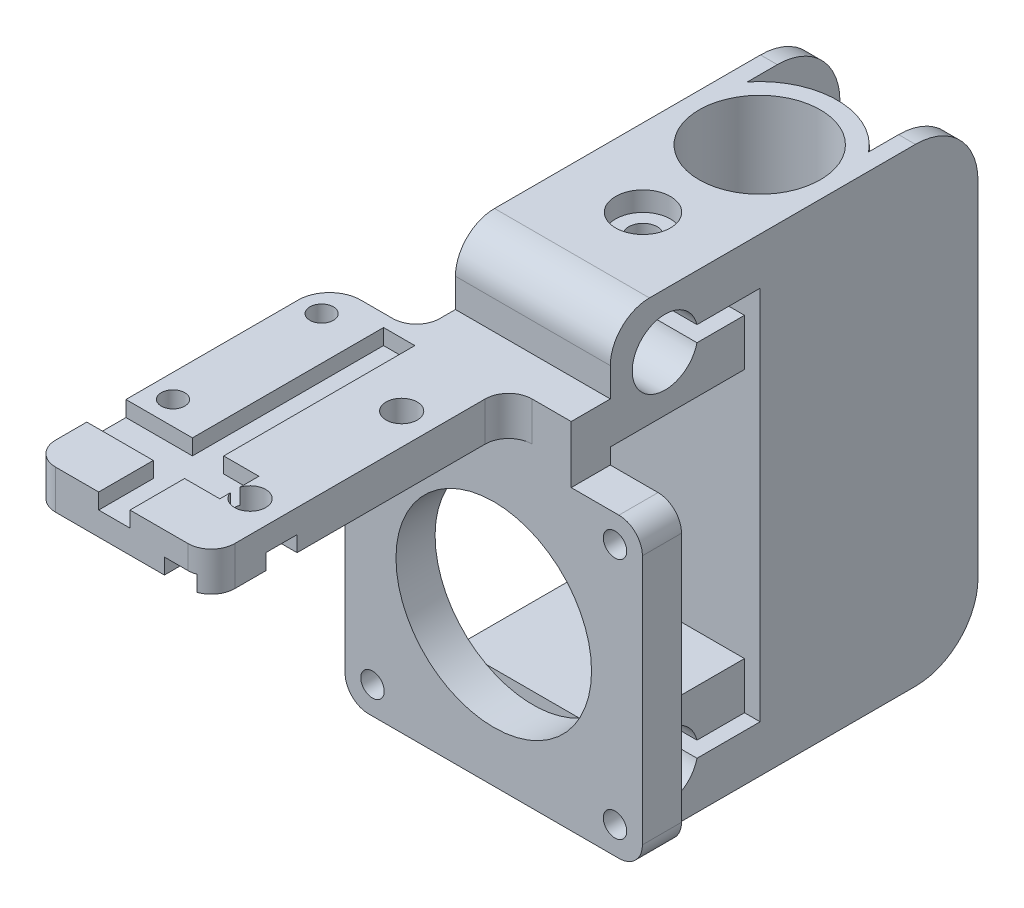
SolidWorks part; units mm, degrees
ref_plane "Спереди" through (0, 0, 0) normal (0, 0, 1) x (1, 0, 0)
ref_plane "Сверху" through (0, 0, 0) normal (0, 1, 0) x (1, 0, 0)
ref_plane "Справа" through (0, 0, 0) normal (1, 0, 0) x (0, 0, -1)
sketch "Эскиз1" plane through (0, 0, 0) normal (0, 1, 0) x (1, 0, 0)
  line L0 (9.9, 0) -> (9.9, 18)
  line L1 (9.9, 18) -> (-9.9, 18)
  line L2 (-9.9, 18) -> (-9.9, 0)
  line L3 (-9.9, 0) -> (-9.9, -29)
  line L4 (-9.9, -29) -> (9.9, -29)
  line L5 (9.9, -29) -> (9.9, 0)
  line L7 (-7.75, -23.1528) -> (7.75, -23.1528)
  line L8 (-7.75, -23.1528) -> (-7.75, 14)
  line L9 (-7.75, 14) -> (7.75, 14)
  line L10 (7.75, -23.1528) -> (7.75, 14)
  line L11 (-7.75, -9.9) -> (7.75, -9.9)
  line L12 (-7.75, -9.9) -> (-7.75, -11.85)
  line L13 (-7.75, -11.85) -> (7.75, -11.85)
  line L14 (7.75, -9.9) -> (7.75, -11.85)
  circle A0 centre (0, 0) radius 7.75
  circle A2 centre (0, 0) radius 9.9
  point P18 (0, -9.9)
  dimension "D1" = 15.5
  dimension "D2" = 19.8
  dimension "D4" = 2.15
  dimension "D3" = 18
  dimension "D5" = 1.95
  dimension "D6" = 47
  dimension "D7" = 4
extrude "Бобышка-Вытянуть1" add sketch "Эскиз1" along normal blind 60 contours L10 A2 L8 A0 | A2 L0 L1 L2 L8 L9 L10 | L10 A2 | L8 A2 | A2 L10 A0 L8 | A2 L10 L7 L8 L3 L4 L5 | L13 L8 L7 L10 | L8 L13 L10 L11 | A2 L11 L10 | A2 L8 L11
sketch "Эскиз2" plane through (9.9, 0, 0) normal (1, 0, 0) x (0, 0, -1)
  line L0 (-29, 60) -> (-29, 0) construction
  line L1 (-29, 60) -> (18, 60) construction
  line L2 (-29, 0) -> (18, 0) construction
  circle A0 centre (-22, 53) radius 4.2
  circle A1 centre (-22, 7) radius 4.2
  dimension "D1" = 8.4
  dimension "D2" = 7
  dimension "D3" = 7
  dimension "D4" = 7
extrude "Вырез-Вытянуть1" cut sketch "Эскиз2" against normal blind 90
sketch "Эскиз3" plane through (9.9, 0, 0) normal (1, 0, 0) x (0, 0, -1)
  line L1 (-29, 60) -> (-29, 0) construction
  line L2 (-29, 0) -> (18, 0) construction
  line L3 (-29, 60) -> (18, 60) construction
  line L5 (-33.0715, 30) -> (18, 30) construction
  line L10 (18, 60) -> (18, 0) construction
  line L26 (-22, 6) -> (-9.85, 6)
  line L27 (-22, 6) -> (-22, 8)
  line L28 (-22, 8) -> (-9.85, 8)
  line L29 (-9.85, 6) -> (-9.85, 8)
  line L30 (-22, 52) -> (-9.85, 52)
  line L31 (-22, 52) -> (-22, 54)
  line L32 (-22, 54) -> (-9.85, 54)
  line L33 (-9.85, 52) -> (-9.85, 54)
  line L34 (-9.85, 6) -> (-11.85, 6)
  line L35 (-9.85, 6) -> (-9.85, 54)
  line L36 (-9.85, 54) -> (-11.85, 54)
  line L37 (-11.85, 6) -> (-11.85, 54)
  line L38 (-9.85, 14) -> (-29, 14)
  line L39 (-9.85, 14) -> (-9.85, 46)
  line L40 (-9.85, 46) -> (-29, 46)
  line L41 (-29, 14) -> (-29, 46)
  circle A1 centre (-22, 7) radius 4.2 construction
  circle A2 centre (-22, 53) radius 4.2 construction
  point P2 (-22, 7)
  point P7 (-22, 53)
  dimension "D2" = 14
  dimension "D3" = 14
  dimension "D4" = 17.15
  dimension "D8" = 2
  dimension "D9" = 2
  dimension "D10" = 2
extrude "Вырез-Вытянуть2" cut sketch "Эскиз3" against normal blind 40
sketch "Эскиз4" plane through (0, 0, -18) normal (0, 0, -1) x (-1, 0, 0)
  line L0 (-9.9, 60) -> (9.9, 60) construction
  line L1 (-7.75, 60) -> (7.75, 60)
  line L2 (-7.75, 60) -> (-7.75, 40.5)
  line L3 (-7.75, 26.5) -> (7.75, 26.5)
  line L4 (7.75, 60) -> (7.75, 40.5)
  line L5 (-9.9, 0) -> (9.9, 0) construction
  line L6 (7.75, 26.5) -> (7.75, 33.5)
  line L7 (7.75, 33.5) -> (-7.75, 33.5)
  line L9 (7.75, 40.5) -> (-7.75, 40.5)
  line L10 (-7.75, 0) -> (7.75, 0)
  line L11 (-7.75, 0) -> (-7.75, 19.5)
  line L12 (-7.75, 19.5) -> (7.75, 19.5)
  line L13 (7.75, 0) -> (7.75, 19.5)
  line L14 (7.75, 26.5) -> (7.75, 33.5)
  line L15 (-7.75, 60) -> (-7.75, 40.5)
  line L16 (7.75, 40.5) -> (7.75, 60)
  line L17 (-7.75, 33.5) -> (-7.75, 26.5)
  line L18 (-7.75, 33.5) -> (-7.75, 26.5)
  line L19 (7.75, 33.5) -> (7.75, 26.5)
  line L20 (9.9, 60) -> (9.9, 0) construction
  point P20 (7.75, 30)
  point P23 (9.9, 30)
  line M9 (-9.9, 0) -> (9.9, 0)
  line M11 (9.9, 60) -> (-9.9, 60)
  dimension "D1" = 7
  dimension "D2" = 7
  dimension "D4" = 7
extrude "Вырез-Вытянуть3" cut sketch "Эскиз4" against normal blind 6 contours L4 L2 L3 M11 | L13 L12 L11 M9 | L7 L17 L3 L6
fillet "Скругление1" radius 5 2 edges at (0, 60, 29) (0, 0, 29)
fillet "Скругление2" radius 8 4 edges at (8.825, 0, -18) (-8.825, 0, -18) (-8.825, 60, -18) (8.825, 60, -18)
sketch "Эскиз13" plane through (0, 0, 0) normal (0, -1, 0) x (1, 0, 0)
  circle A0 centre (0, 14.9208) radius 1.8
  dimension "D1" = 3.6
  dimension "D2" = 3
extrude "Вырез-Вытянуть9" cut sketch "Эскиз13" against normal blind 75
sketch "Эскиз8" plane through (0, 0, 29) normal (0, 0, 1) x (1, 0, 0)
  line L0 (-9.9, 55) -> (-9.9, 46) construction
  line L1 (-19, 44) -> (19, 44)
  line L2 (-19, 44) -> (-19, 6)
  line L3 (-19, 6) -> (19, 6)
  line L4 (19, 44) -> (19, 6)
  line L5 (-9.9, 5) -> (9.9, 5) construction
  line L6 (9.9, 0) -> (-9.9, 0) construction
  line L7 (9.9, 44) -> (-9.9, 44)
  line L8 (9.9, 44) -> (9.9, 51.3151)
  line L9 (9.9, 51.3151) -> (-9.9, 51.3151)
  line L10 (-9.9, 44) -> (-9.9, 51.3151)
  line L11 (9.9, 55) -> (9.9, 46) construction
  point P4 (0, 6)
  point P7 (0, 5)
  line M13 (-9.9, 14) -> (-9.9, 5)
  line M15 (9.9, 5) -> (9.9, 14)
  line M16 (9.9, 14) -> (-9.9, 14)
  dimension "D1" = 38
  dimension "D2" = 38
  dimension "D3" = 6
extrude "Бобышка-Вытянуть3" add sketch "Эскиз8" along normal blind 5 contours L4 L1 L2 L3 M13 M16 M15 | L10 L1 L8 L9 | L3 M13 M15 M16
sketch "Эскиз10" plane through (0, 0, 34) normal (0, 0, 1) x (1, 0, 0)
  line L2 (-19, 44) -> (-19, 6) construction
  line L3 (-19, 6) -> (19, 6) construction
  line L4 (-15.5, 9.5) -> (-15.5, 40.5) construction
  line L5 (-15.5, 40.5) -> (15.5, 40.5) construction
  line L6 (15.5, 40.5) -> (15.5, 9.5) construction
  line L7 (15.5, 9.5) -> (-15.5, 9.5) construction
  circle A0 centre (0, 25) radius 12.5
  circle A1 centre (-15.5, 9.5) radius 1.5
  circle A2 centre (15.5, 9.5) radius 1.5
  circle A3 centre (-15.5, 40.5) radius 1.5
  circle A4 centre (15.5, 40.5) radius 1.5
  point P11 (0, 9.5)
  point P14 (-19, 25)
  point P15 (15.5, 25)
  point P17 (0, 6)
  dimension "D1" = 25
  dimension "D2" = 3
  dimension "D3" = 31
  dimension "D4" = 31
extrude "Вырез-Вытянуть6" cut sketch "Эскиз10" against normal up to vertex (5 mm away) contours A0 | A1 | A3 | A2 | A4 up to point (19, 6, 29)
fillet "Скругление4" radius 3 4 edges at (19, 44, 31.5) (-19, 44, 31.5) (-19, 6, 31.5) (19, 6, 31.5)
sketch "Эскиз14" plane through (0, 14, 0) normal (0, 1, 0) x (1, 0, 0)
  line L0 (-9.9, -11.85) -> (9.9, -11.85) construction
  line L1 (-1.7729, -17.9916) -> (1.7729, -17.9916)
  line L2 (1.7729, -17.9916) -> (3.5458, -14.9208)
  line L3 (3.5458, -14.9208) -> (1.7729, -11.85)
  line L4 (1.7729, -11.85) -> (-1.7729, -11.85)
  line L5 (-1.7729, -11.85) -> (-3.5458, -14.9208)
  line L6 (-3.5458, -14.9208) -> (-1.7729, -17.9916)
  circle A0 centre (0, -14.9208) radius 3.0708 construction
extrude "Вырез-Вытянуть10" cut sketch "Эскиз14" against normal blind 2 and the other way blind 34
sketch "Эскиз15" plane through (0, 60, 0) normal (0, 1, 0) x (1, 0, 0)
  circle A0 centre (0, -14.9208) radius 3.5
  dimension "D1" = 7
extrude "Вырез-Вытянуть11" cut sketch "Эскиз15" against normal blind 2.5
sketch "Эскиз16" plane through (0, 0, 0) normal (0, -1, 0) x (1, 0, 0)
  circle A0 centre (0, 14.9208) radius 3.5
  dimension "D1" = 7
extrude "Вырез-Вытянуть12" cut sketch "Эскиз16" against normal blind 2.5
sketch "Эскиз17" plane through (0, 0, 34) normal (0, 0, 1) x (1, 0, 0)
  line L1 (1.9, 51.3151) -> (-21, 51.3151)
  line L2 (1.9, 51.3151) -> (1.9, 46.3151)
  line L3 (1.9, 46.3151) -> (-21, 46.3151)
  line L4 (-21, 51.3151) -> (-21, 46.3151)
  line L5 (-19, 41) -> (-19, 9) construction
  line L6 (9.9, 51.3151) -> (-9.9, 51.3151) construction
  line L7 (9.9, 44) -> (9.9, 51.3151) construction
  dimension "D1" = 5
  dimension "D2" = 2
  dimension "D3" = 8
extrude "Бобышка-Вытянуть4" add sketch "Эскиз17" along normal blind 38
sketch "Эскиз18" plane through (0, 51.3151, 0) normal (0, 1, 0) x (1, 0, 0)
  line L0 (-9.9, -34) -> (-21, -34) construction
  line L1 (-21, -72) -> (-21, -34) construction
  line L2 (1.9, -72) -> (1.9, -34) construction
  circle A0 centre (-18, -57) radius 1.5
  circle A1 centre (-18, -38) radius 1.5
  circle A2 centre (-2.1, -63.0448) radius 2
  circle A3 centre (-2.1, -43.673) radius 2
  dimension "D1" = 19
  dimension "D4" = 3
  dimension "D5" = 4
  dimension "D2" = 4
  dimension "D3" = 3
  dimension "D6" = 4
extrude "Вырез-Вытянуть13" cut sketch "Эскиз18" against normal blind 36.5
sketch "Эскиз19" plane through (0, 46.3151, 0) normal (0, -1, 0) x (1, 0, 0)
  line L1 (-18, 61.0415) -> (-21.5, 59.0207)
  line L2 (-21.5, 59.0207) -> (-21.5, 54.9793)
  line L3 (-21.5, 54.9793) -> (-18, 52.9585)
  line L4 (-18, 52.9585) -> (-14.5, 54.9793)
  line L5 (-14.5, 54.9793) -> (-14.5, 59.0207)
  line L6 (-14.5, 59.0207) -> (-18, 61.0415)
  line L7 (-18, 42.0415) -> (-21.5, 40.0207)
  line L8 (-21.5, 40.0207) -> (-21.5, 35.9793)
  line L9 (-21.5, 35.9793) -> (-18, 33.9585)
  line L10 (-18, 33.9585) -> (-14.5, 35.9793)
  line L11 (-14.5, 35.9793) -> (-14.5, 40.0207)
  line L12 (-14.5, 40.0207) -> (-18, 42.0415)
  line L13 (-21, 72) -> (-21, 34) construction
  circle A0 centre (-18, 57) radius 3.5 construction
  circle A1 centre (-18, 38) radius 3.5 construction
  dimension "D1" = 7
extrude "Вырез-Вытянуть14" cut sketch "Эскиз19" against normal blind 2
fillet "Скругление5" radius 3 4 edges at (-21, 48.8151, 72) (1.9, 48.8151, 72) (1.9, 48.8151, 34) (-9.9, 48.8151, 34)
sketch "Эскиз20" plane through (0, 51.3151, 0) normal (0, 1, 0) x (1, 0, 0)
  line L0 (-1.1, -72) -> (-18, -72) construction
  line L1 (-8.5, -72) -> (-12.5, -72)
  line L2 (-8.5, -72) -> (-8.5, -35.5865)
  line L3 (-8.5, -35.5865) -> (-12.5, -35.5865)
  line L4 (-12.5, -72) -> (-12.5, -35.5865)
  line L5 (-21, -69) -> (-21, -34) construction
  line L6 (-4, -65.0182) -> (-21, -65.0182)
  line L7 (-4, -65.0182) -> (-4, -60.0182)
  line L8 (-4, -60.0182) -> (-21, -60.0182)
  line L9 (-21, -65.0182) -> (-21, -60.0182)
  line L11 (-12.9, -34) -> (-21, -34) construction
  point P14 (-16.95, -34)
  line M10 (-21, -34) -> (-21, -69)
  line M12 (-18, -72) -> (-1.1, -72)
  dimension "D1" = 31.0182
  dimension "D2" = 5
  dimension "D3" = 8.5
  dimension "D4" = 4
  dimension "D5" = 17
extrude "Вырез-Вытянуть15" cut sketch "Эскиз20" against normal blind 2 contours L7 L8 L2 L6 | L2 L8 L4 L6 | L4 L8 L6 M10 | L2 L6 L4 M12 | L8 L2 L3 L4
fillet "Скругление6" radius 4 1 edges at (-21, 48.8151, 34)
sketch "Эскиз22" plane through (0, 46.3151, 0) normal (0, -1, 0) x (1, 0, 0)
  line L0 (1.9, 69) -> (1.9, 37) construction
  line L1 (-2.1, 65.0448) -> (1.9, 65.0448)
  line L2 (-2.1, 65.0448) -> (-2.1, 61.0448)
  line L3 (-2.1, 61.0448) -> (1.9, 61.0448)
  line L4 (1.9, 65.0448) -> (1.9, 61.0448)
  line L5 (-18, 72) -> (-1.1, 72) construction
  line L6 (-2.1, 45.673) -> (1.9, 45.673)
  line L7 (-2.1, 45.673) -> (-2.1, 41.673)
  line L8 (-2.1, 41.673) -> (1.9, 41.673)
  line L9 (1.9, 45.673) -> (1.9, 41.673)
  line L10 (-4.1, 72) -> (-0.1, 72)
  line L11 (-4.1, 72) -> (-4.1, 63.0448)
  line L12 (-4.1, 63.0448) -> (-0.1, 63.0448)
  line L13 (-0.1, 72) -> (-0.1, 63.0448)
  circle A0 centre (-2.1, 63.0448) radius 2 construction
  circle A1 centre (-2.1, 43.673) radius 2 construction
  circle M4 centre (-2.1, 63.0448) radius 2
  line M13 (1.9, 37) -> (1.9, 69)
  arc M14 (1.9, 69) -> (-1.1, 72) centre (-1.1, 69) ccw
  line M15 (-1.1, 72) -> (-18, 72)
extrude "Вырез-Вытянуть16" cut sketch "Эскиз22" against normal blind 2 contours L11 L1 M15 M4 M13 M14 | L12 L3 M4 M13 | L13 L1 M4
